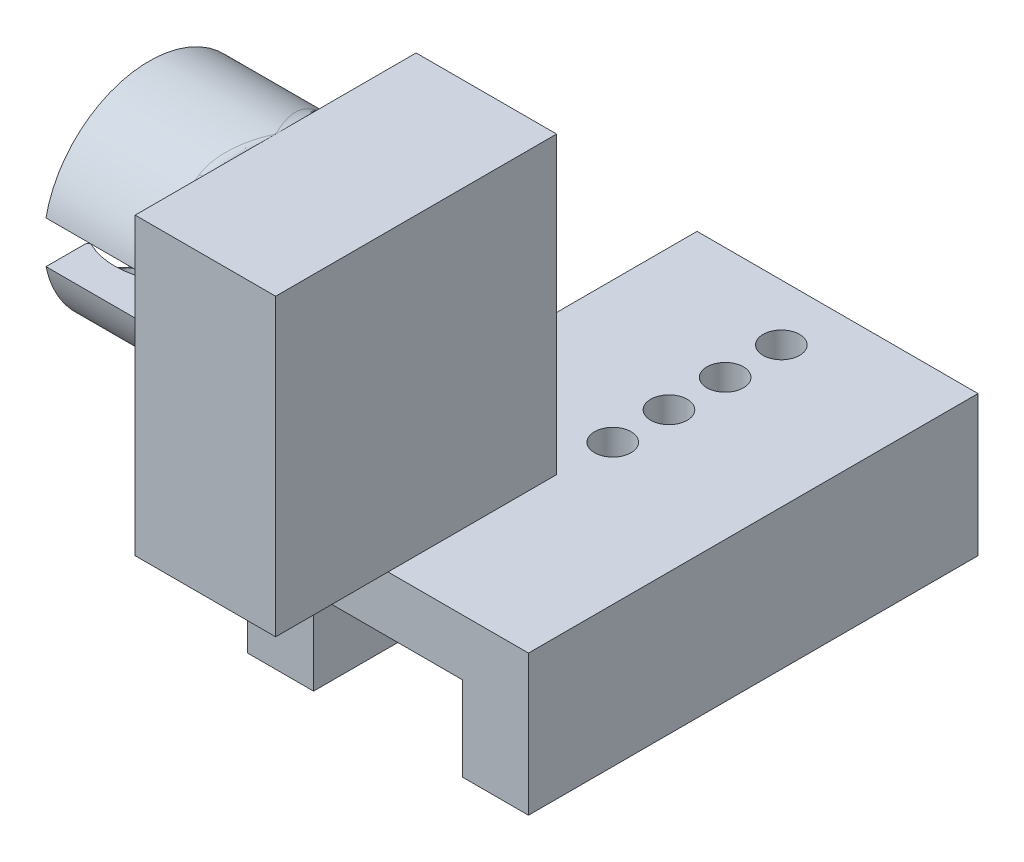
SolidWorks part; units mm, degrees
ref_plane "Front Plane" through (0, 0, 0) normal (0, 0, 1) x (1, 0, 0)
ref_plane "Top Plane" through (0, 0, 0) normal (0, 1, 0) x (1, 0, 0)
ref_plane "Right Plane" through (0, 0, 0) normal (1, 0, 0) x (0, 0, -1)
sketch "Sketch1" plane through (0, 0, 0) normal (0, 1, 0) x (1, 0, 0)
  line L1 (-5, 8) -> (5, 8)
  line L2 (-5, 8) -> (-5, -8)
  line L3 (-5, -8) -> (5, -8)
  line L4 (5, 8) -> (5, -8)
  line L5 (-5, 8) -> (5, -8) construction
  line L6 (-5, -8) -> (5, 8) construction
  point P0 (0, 0)
  dimension "D1" = 10
  dimension "D2" = 16
extrude "Base Extrude" add sketch "Sketch1" along normal blind 2
sketch "Sketch2" plane through (0, 0, 0) normal (0, -1, 0) x (1, 0, 0)
  line L0 (-5, 8) -> (5, 8) construction
  line L1 (5, -8) -> (2.65, -8)
  line L2 (5, -8) -> (5, 8)
  line L3 (5, 8) -> (2.65, 8)
  line L4 (2.65, -8) -> (2.65, 8)
  line L6 (-5, -8) -> (-2.65, -8)
  line L7 (-5, -8) -> (-5, 8)
  line L8 (-5, 8) -> (-2.65, 8)
  line L9 (-2.65, -8) -> (-2.65, 8)
  dimension "D1" = 2.35
extrude "Side Rails" add sketch "Sketch2" along normal blind 3
sketch "Sketch3" plane through (0, 2, 0) normal (0, 1, 0) x (1, 0, 0)
  line L5 (-5, 8) -> (-5, -8) construction
  line L6 (-5, -2) -> (0, -2)
  line L7 (-5, -2) -> (-5, -12)
  line L8 (-5, -12) -> (0, -12)
  line L9 (0, -2) -> (0, -12)
  dimension "D1" = 5
  dimension "D2" = 10
  dimension "D3" = 6
extrude "Ball Joint Post" add sketch "Sketch3" along normal blind 10.5
sketch "Sketch4" plane through (-5, 0, 0) normal (-1, 0, 0) x (0, 0, 1)
  line L0 (7, 12.5) -> (7, 8.75) construction
  line L1 (2, 12.5) -> (12, 12.5) construction
  circle A0 centre (7, 8.75) radius 3.75
  dimension "D1" = 3.75
extrude "Boss-Extrude1" add sketch "Sketch4" along normal blind 4.5
ref_plane "Plane1" through (-8.3, 0, 0) normal (-1, 0, 0) x (0, 0, 1)
sketch "Sketch6" plane through (-8.3, 0, 0) normal (-1, 0, 0) x (0, 0, 1)
  line L0 (7, 6.2) -> (7, 11.3)
  circle A0 centre (7, 8.75) radius 2.55
  dimension "D1" = 5.1
revolve "Cut-Revolve2" cut sketch "Sketch6" angle 360 about L0 region at (-8.3, 8.75, 5.9177) reverse direction yes
sketch "Sketch7" plane through (-5, 0, 0) normal (-1, 0, 0) x (0, 0, 1)
  line L0 (7, 12.5) -> (7, 8.75) construction
  line L1 (2, 12.5) -> (2, 2) construction
  line L2 (12, 8) -> (2, 8)
  line L3 (12, 8) -> (12, 9.5)
  line L4 (12, 9.5) -> (2, 9.5)
  line L5 (2, 8) -> (2, 9.5)
  line L6 (12, 8) -> (2, 9.5) construction
  line L7 (12, 9.5) -> (2, 8) construction
  dimension "D1" = 3.75
  dimension "D2" = 1.5
extrude "Cut-Extrude2" cut sketch "Sketch7" along normal up to surface (4.5 mm away) up to face at (-9.5, 8.75, 9.25)
fillet "Fillet1" radius 0.1 2 edges at (-9.5, 11, 7) (-9.5, 6.5, 7)
fillet "Fillet2" radius 0.7 5 edges at (-5, 11.6547, 4.6283) (-5, 9.5, 7) (-5, 8, 7) (-5, 11.6547, 9.3717) (-5, 5, 7)
sketch "Sketch8" plane through (0, 2, 0) normal (0, 1, 0) x (1, 0, 0)
  circle A0 centre (0, 6) radius 0.65
  circle A1 centre (0, 4) radius 0.65
  circle A2 centre (0, 2) radius 0.65
  circle A3 centre (0, 0) radius 0.65
  dimension "D3" = 1.3
  dimension "D1" = 2
  dimension "D2" = 5
  dimension "D5" = 2
  dimension "D4" = 4
extrude "Cut-Extrude3" cut sketch "Sketch8" against normal up to surface (2 mm away) up to face at (0, 0, 0)
